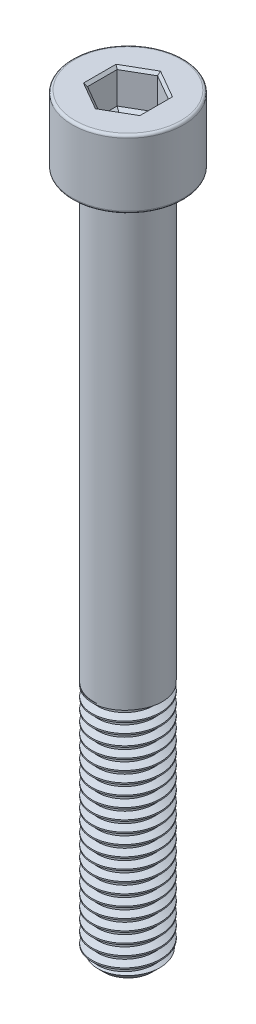
SolidWorks part; units mm, degrees
material "AISI Type A2 Tool Steel"
ref_plane "Front Plane" through (0, 0, 0) normal (0, 0, 1) x (1, 0, 0)
ref_plane "Top Plane" through (0, 0, 0) normal (0, 1, 0) x (1, 0, 0)
ref_plane "Right Plane" through (0, 0, 0) normal (1, 0, 0) x (0, 0, -1)
sketch "Sketch1" plane through (0, 0, 0) normal (0, 1, 0) x (1, 0, 0)
  circle A0 centre (0, 0) radius 4
  dimension "D1" = 8
extrude "Boss-Extrude1" add sketch "Sketch1" along normal blind 28
thread "Thread1" pitch 1.25 method cut profile "Thread Profile1" start angle 0, offset 2, length 0, pitch 1.25, diameter 8
ref_plane "Plane1" through (-4, 30, 0) normal (0, 0, 1) x (-1, 0, 0)
sketch "Thread Profile1" plane through (-4, 30, 0) normal (0, 0, 1) x (-1, 0, 0)
  line L0 (0, 0) -> (0, 1.25) construction
  line L11 (0, 0) -> (0, 1.0937)
  line L12 (0, 1.0937) -> (-0.6766, 0.7031)
  line L13 (-0.6766, 0.7031) -> (-0.6766, 0.3906)
  line L15 (-0.6766, 0.3906) -> (0, 0)
  line L17 (-0.6766, 0.5469) -> (0, 0.5469) construction
  point P2 (0, 0)
  dimension "Pitch" = 1.25
  dimension "Profile_Angle" = 60
  dimension "Profile_Land" = 0.3125
  dimension "Profile_Height" = 0.6766
sketch "Sketch2" plane through (0, 28, 0) normal (0, 1, 0) x (1, 0, 0)
  circle A0 centre (0, 0) radius 4
  dimension "D1" = 8
extrude "Boss-Extrude2" add sketch "Sketch2" along normal blind 52
sketch "Sketch5" plane through (0, 80, 0) normal (0, 1, 0) x (1, 0, 0)
  circle A0 centre (0, 0) radius 6.5
  dimension "D1" = 13
extrude "Boss-Extrude3" add sketch "Sketch5" along normal blind 8
sketch "Sketch6" plane through (0, 0, 0) normal (0, 0, 1) x (1, 0, 0)
  line L0 (0, 0) -> (0, 0.7245) construction
  line L1 (0, 0) -> (4.01, 0) construction
  line L2 (4.01, 0) -> (4.01, 1.2)
  line L3 (4.01, 1.2) -> (2.81, 0)
  line L4 (2.81, 0) -> (4.01, 0)
  dimension "D1" = 1.2
  dimension "D2" = 45
  dimension "D3" = 4.01
revolve "Cut-Revolve1" cut sketch "Sketch6" angle 360 about L0
fillet "Fillet1" radius 0.3 2 edges at (0, 80, 6.5) (0, 88, 6.5)
sketch "Sketch7" plane through (0, 88, 0) normal (0, 1, 0) x (1, 0, 0)
  line L1 (0, 3.4641) -> (-3, 1.7321)
  line L2 (-3, 1.7321) -> (-3, -1.7321)
  line L3 (-3, -1.7321) -> (0, -3.4641)
  line L4 (0, -3.4641) -> (3, -1.7321)
  line L5 (3, -1.7321) -> (3, 1.7321)
  line L6 (3, 1.7321) -> (0, 3.4641)
  circle A0 centre (0, 0) radius 3 construction
  dimension "D1" = 6
extrude "Cut-Extrude1" cut sketch "Sketch7" against normal blind 4
chamfer "Chamfer1" distance 0.3 angle 45 6 edges at (-3, 88, 0) (-1.5, 88, 2.5981) (1.5, 88, 2.5981) (3, 88, 0) (1.5, 88, -2.5981) (-1.5, 88, -2.5981)
sketch "Sketch8" plane through (0, 84, 0) normal (0, 1, 0) x (1, 0, 0)
  line L1 (0, 3.4641) -> (-3, 1.7321)
  line L2 (-3, 1.7321) -> (-3, -1.7321)
  line L3 (-3, -1.7321) -> (0, -3.4641)
  line L4 (0, -3.4641) -> (3, -1.7321)
  line L5 (3, -1.7321) -> (3, 1.7321)
  line L6 (3, 1.7321) -> (0, 3.4641)
  circle A0 centre (0, 0) radius 3 construction
extrude "Cut-Extrude2" cut sketch "Sketch8" against normal blind 0.4 draft 60
